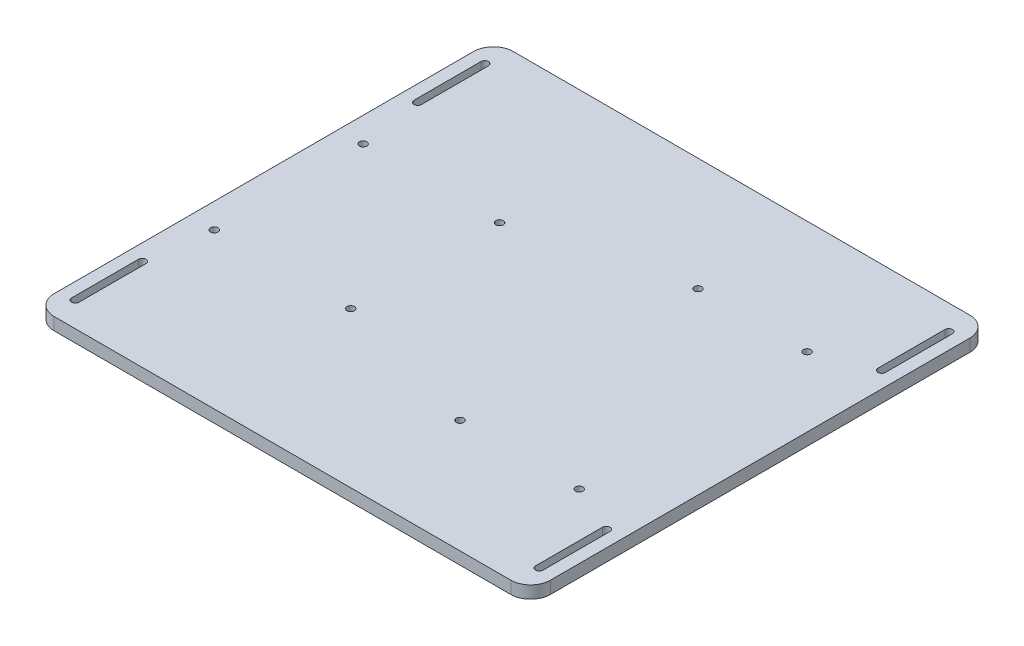
SolidWorks part; units mm, degrees
ref_plane "Front Plane" through (0, 0, 0) normal (0, 0, 1) x (1, 0, 0)
ref_plane "Top Plane" through (0, 0, 0) normal (0, 1, 0) x (1, 0, 0)
ref_plane "Right Plane" through (0, 0, 0) normal (1, 0, 0) x (0, 0, -1)
sketch "Sketch2" plane through (0, 0, 0) normal (0, 1, 0) x (1, 0, 0)
  line L0 (-93.5, 55.5) -> (-93.5, 82.5) construction
  line L1 (-100, -92.5) -> (100, -92.5)
  line L2 (-100, -92.5) -> (-100, 92.5)
  line L3 (-100, 92.5) -> (100, 92.5)
  line L4 (100, -92.5) -> (100, 92.5)
  line L5 (-100, -92.5) -> (100, 92.5) construction
  line L6 (-100, 92.5) -> (100, -92.5) construction
  line L7 (-95, 55.5) -> (-95, 82.5)
  line L8 (-92, 55.5) -> (-92, 82.5)
  line L9 (-100, 0) -> (100, 0) construction
  line L10 (100, 0) -> (0, 92.5) construction
  line L11 (0, 92.5) -> (0, -92.5) construction
  line L12 (93.5, 55.5) -> (93.5, 82.5) construction
  line L13 (95, 55.5) -> (95, 82.5)
  line L14 (92, 55.5) -> (92, 82.5)
  line L15 (93.5, -55.5) -> (93.5, -82.5) construction
  line L16 (95, -55.5) -> (95, -82.5)
  line L17 (92, -55.5) -> (92, -82.5)
  line L18 (-93.5, -55.5) -> (-93.5, -82.5) construction
  line L19 (-95, -55.5) -> (-95, -82.5)
  line L20 (-92, -55.5) -> (-92, -82.5)
  arc A0 (-95, 55.5) -> (-92, 55.5) centre (-93.5, 55.5) ccw
  arc A1 (-92, 82.5) -> (-95, 82.5) centre (-93.5, 82.5) ccw
  arc A2 (95, 55.5) -> (92, 55.5) centre (93.5, 55.5) cw
  arc A3 (92, 82.5) -> (95, 82.5) centre (93.5, 82.5) cw
  arc A4 (95, -55.5) -> (92, -55.5) centre (93.5, -55.5) ccw
  arc A5 (92, -82.5) -> (95, -82.5) centre (93.5, -82.5) ccw
  arc A6 (-95, -55.5) -> (-92, -55.5) centre (-93.5, -55.5) cw
  arc A7 (-92, -82.5) -> (-95, -82.5) centre (-93.5, -82.5) cw
  point P0 (0, 0)
  point P8 (-93.5, 69)
  point P19 (93.5, 69)
  point P26 (93.5, -69)
  point P33 (-93.5, -69)
  dimension "D4" = 1.5
  dimension "D1" = 200
  dimension "D2" = 185
  dimension "D3" = 27
  dimension "D5" = 5
  dimension "D6" = 10
extrude "Boss-Extrude1" add sketch "Sketch2" along normal blind 5
sketch "Sketch3" plane through (0, 5, 0) normal (0, 1, 0) x (1, 0, 0)
  line L0 (-100, 0) -> (100, 0) construction
  line L1 (-100, 92.5) -> (-100, -92.5) construction
  line L2 (100, -92.5) -> (100, 92.5) construction
  line L3 (100, 0) -> (0, -92.5) construction
  line L4 (-100, -92.5) -> (100, -92.5) construction
  line L5 (0, -92.5) -> (0, 92.5) construction
  line L6 (100, 92.5) -> (-100, 92.5) construction
  line L7 (-62.5, -35) -> (-62.5, 55.3864) construction
  line L8 (-30, -35) -> (-95, -35)
  line L9 (-30, -35) -> (-30, 35)
  line L10 (-30, 35) -> (-95, 35)
  line L11 (-95, -35) -> (-95, 35)
  line L12 (-30, -35) -> (-95, 35) construction
  line L13 (-30, 35) -> (-95, -35) construction
  circle A0 centre (-90, -30) radius 1.5
  circle A1 centre (-90, 30) radius 1.5
  circle A2 centre (-35, 30) radius 1.5
  circle A3 centre (-35, -30) radius 1.5
  point P9 (-62.5, 0)
  dimension "D4" = 3
  dimension "D1" = 65
  dimension "D2" = 70
  dimension "D3" = 5
  dimension "D5" = 5
  dimension "D6" = 5
extrude "Cut-Extrude1" cut sketch "Sketch3" against normal through all contours A0 | A1 | A3 | A2
sketch "Sketch4" plane through (0, 5, 0) normal (0, 1, 0) x (1, 0, 0)
  line L0 (-100, 0) -> (100, 0) construction
  line L1 (-100, 92.5) -> (-100, -92.5) construction
  line L2 (100, -92.5) -> (100, 92.5) construction
  line L3 (50, 92.5) -> (50, -92.5) construction
  line L4 (100, 92.5) -> (-100, 92.5) construction
  line L5 (-100, -92.5) -> (100, -92.5) construction
  circle A0 centre (28, 46.935) radius 1.5
  circle A1 centre (72, 46.935) radius 1.5
  circle A2 centre (26, -46.935) radius 1.5
  circle A3 centre (74, -46.935) radius 1.5
  dimension "D1" = 3
  dimension "D4" = 3
  dimension "D7" = 46.935
  dimension "D2" = 50
  dimension "D3" = 44
  dimension "D5" = 48
  dimension "D6" = 93.87
extrude "Cut-Extrude3" cut sketch "Sketch4" against normal through all
fillet "Fillet1" radius 8 4 edges at (100, 2.5, -92.5) (100, 2.5, 92.5) (-100, 2.5, -92.5) (-100, 2.5, 92.5)
